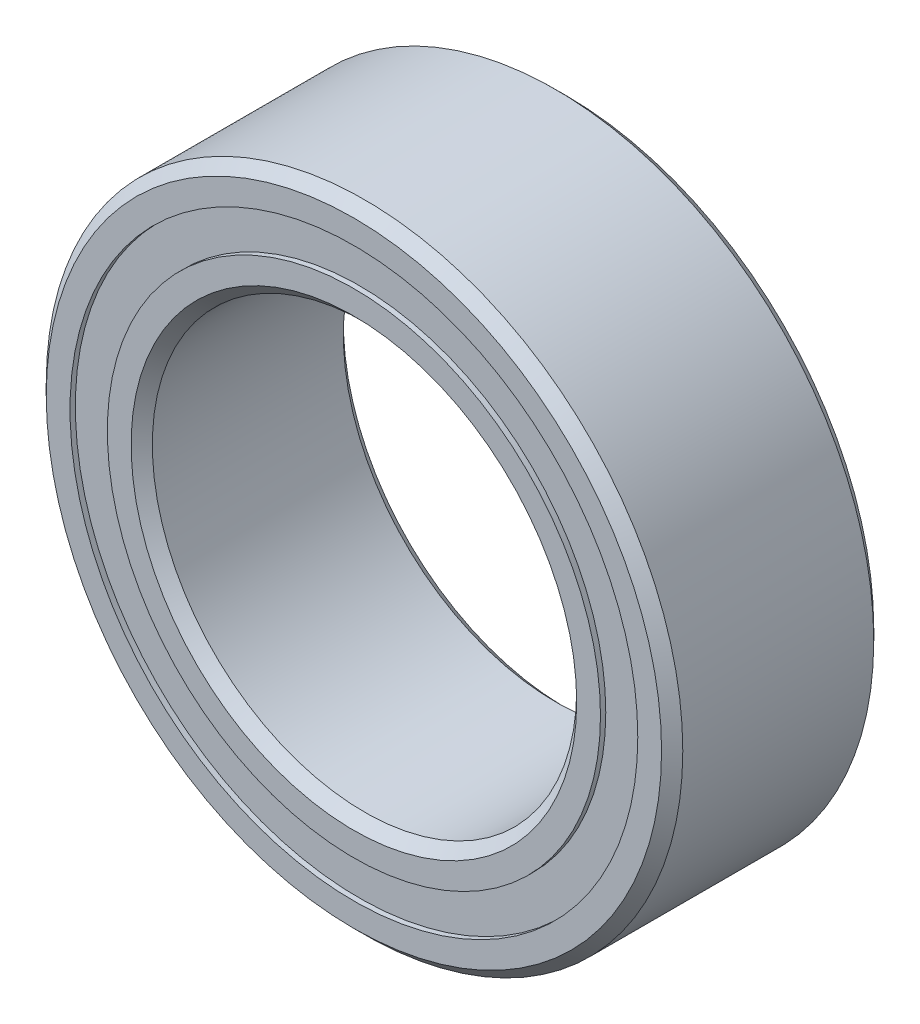
SolidWorks part; units mm, degrees
ref_plane "Front Plane" through (0, 0, 0) normal (0, 0, 1) x (1, 0, 0)
ref_plane "Top Plane" through (0, 0, 0) normal (0, 1, 0) x (1, 0, 0)
ref_plane "Right Plane" through (0, 0, 0) normal (1, 0, 0) x (0, 0, -1)
sketch "Sketch1" plane through (0, 0, 0) normal (1, 0, 0) x (0, 0, -1)
  line L0 (-1.5875, 0) -> (1.5875, 0) construction
  line L1 (0, 4.7625) -> (0, -4.7625) construction
  line L2 (1.4288, 4.7625) -> (-1.4288, 4.7625)
  line L3 (-1.4288, 4.7625) -> (-1.5875, 4.6037)
  line L4 (-1.5875, 4.6037) -> (-1.5875, 4.2479)
  line L5 (-1.5875, 4.2479) -> (-0.7056, 4.2479)
  line L6 (1.5875, 4.2479) -> (0.7056, 4.2479)
  line L7 (1.5875, 4.6037) -> (1.5875, 4.2479)
  line L8 (1.4288, 4.7625) -> (1.5875, 4.6037)
  line L9 (0, 4.7625) -> (0, 3.9688) construction
  line L10 (0, 3.9688) -> (0, 3.175) construction
  arc A0 (-0.7056, 4.2479) -> (0.7056, 4.2479) centre (0, 3.9688) cw
  point P14 (0, 3.175)
  dimension "Width" = 3.175
  dimension "OD" = 9.525
  dimension "D1" = 45
  dimension "D2" = 0.1588
  dimension "D3" = 1.4111
  dimension "D4" = 0.2791
revolve "Revolve1" add sketch "Sketch1" angle 360 about L0
sketch "Sketch3" plane through (0, 0, 0) normal (1, 0, 0) x (0, 0, -1)
  line L0 (-0.7056, 3.6896) -> (-1.5875, 3.6896)
  line L1 (-1.5875, 4.6037) -> (-1.5875, 4.2479) construction
  line L2 (-1.4288, 4.7625) -> (-1.5875, 4.6037) construction
  line L3 (-1.5875, 3.6896) -> (-1.5875, 3.3337)
  line L5 (-1.5875, 3.3337) -> (-1.4288, 3.175)
  line L6 (-1.4288, 3.175) -> (1.4288, 3.175)
  line L7 (1.4288, 4.7625) -> (1.4288, -4.7625) construction
  line L8 (1.4288, 3.175) -> (1.5875, 3.3337)
  line L9 (1.5875, -4.6037) -> (1.5875, 4.6037) construction
  line L10 (1.5875, 3.3337) -> (1.5875, 3.6896)
  line L11 (1.5875, 3.6896) -> (0.7056, 3.6896)
  line L12 (0, 4.7625) -> (0, -4.7625) construction
  line L13 (1.4288, 4.7625) -> (1.5875, 4.6037) construction
  arc A1 (0.7056, 3.6896) -> (-0.7056, 3.6896) centre (0, 3.9687) cw
  arc A2 (0.7056, 4.2479) -> (-0.7056, 4.2479) centre (0, 3.9688) ccw construction
revolve "Revolve3" add sketch "Sketch3" angle 360 about L0
sketch "Sketch4" plane through (0, 0, 0) normal (1, 0, 0) x (0, 0, -1)
  line L0 (-0.7588, 3.9688) -> (0.7588, 3.9688)
  arc A2 (-0.7588, 3.9688) -> (0.7588, 3.9688) centre (0, 3.9688) cw
  arc A3 (0.7056, 4.2479) -> (-0.7056, 4.2479) centre (0, 3.9688) ccw construction
revolve "Revolve4" add sketch "Sketch4" angle 360 about L0
ref_axis "Axis1" through (0, 0, -1.5875) along (0, 0, 1)
pattern_circular "CirPattern1" count 12 every 30 about axis through (0, 0, -1.5875) along (0, 0, 1) of bodies 104
sketch "Sketch5" plane through (0, 0, 0) normal (1, 0, 0) x (0, 0, -1)
  line L0 (-1.5875, 4.2479) -> (-0.7056, 4.2479) construction
  line L1 (-1.5081, 4.2479) -> (-0.7588, 4.2479)
  line L2 (-1.5081, 4.2479) -> (-1.5081, 3.6896)
  line L3 (-1.5081, 3.6896) -> (-0.7588, 3.6896)
  line L4 (-0.7588, 4.2479) -> (-0.7588, 3.6896)
  line L5 (-0.7056, 3.6896) -> (-1.5875, 3.6896) construction
  line L6 (1.5875, 4.2479) -> (0.7056, 4.2479) construction
  line L7 (1.5081, 4.2479) -> (0.7588, 4.2479)
  line L8 (1.5081, 4.2479) -> (1.5081, 3.6896)
  line L9 (1.5081, 3.6896) -> (0.7588, 3.6896)
  line L10 (0.7588, 4.2479) -> (0.7588, 3.6896)
  line L11 (1.5875, 3.6896) -> (0.7056, 3.6896) construction
  line L12 (-1.4288, 4.7625) -> (-1.5875, 4.6037) construction
  point P18 (-1.5081, 4.6831)
revolve "Revolve5" add sketch "Sketch5" angle 360 about L0
equation "\"D2@Sketch1\" = \"Width@Sketch1\"*.05"
equation "\"D3@Sketch1\" = \"Width@Sketch1\"/2.25"
equation "\"D4@Sketch1\" = (((\"OD@Sketch1\"-\"Width@Sketch1\")/2)/3.25)/3.5"
equation "\"D2@CirPattern1\" = 360/\"Balls@CirPattern1\""
